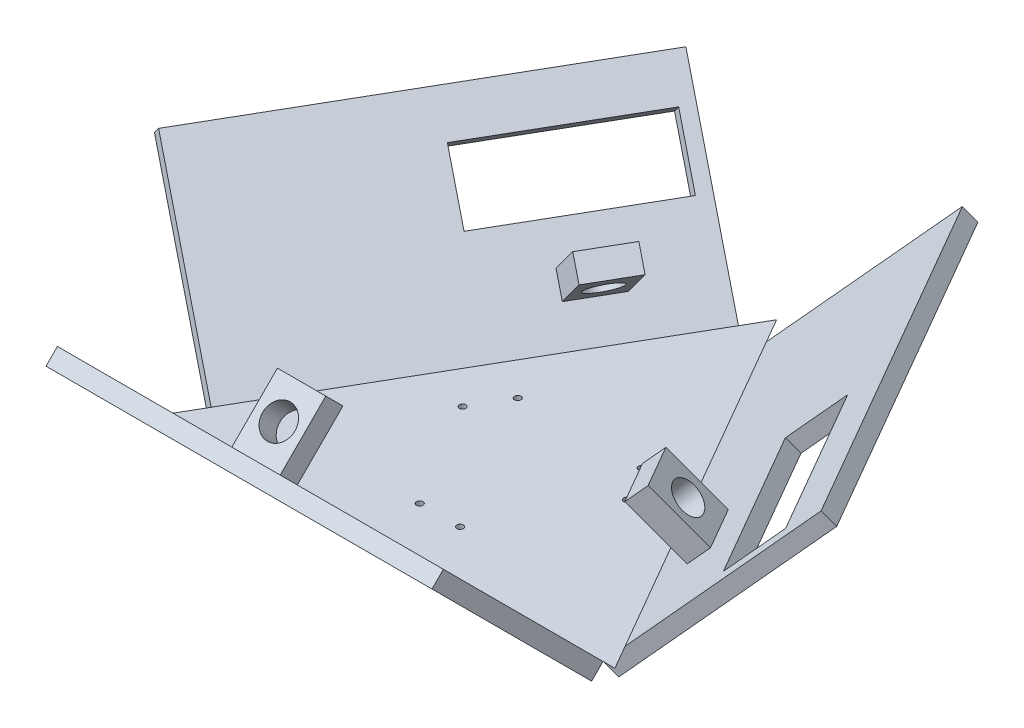
SolidWorks part; units mm, degrees
ref_plane "Front Plane" through (0, 0, 0) normal (0, 0, 1) x (1, 0, 0)
ref_plane "Top Plane" through (0, 0, 0) normal (0, 1, 0) x (1, 0, 0)
ref_plane "Right Plane" through (0, 0, 0) normal (1, 0, 0) x (0, 0, -1)
sketch "Sketch1" plane through (0, 0, 0) normal (0, 1, 0) x (1, 0, 0)
  line L0 (-40, 0) -> (40, 0) construction
  line L1 (-40, 0) -> (0, 69.282) construction
  line L2 (40, 0) -> (0, 69.282) construction
  line L3 (0, 69.282) -> (48.4974, 97.282) construction
  line L4 (40, 0) -> (88.4974, 28) construction
  line L5 (40, 0) -> (40, -56) construction
  line L6 (-40, 0) -> (-40, -56) construction
  line L7 (0, 69.282) -> (-48.4974, 97.282) construction
  line L8 (-40, 0) -> (-88.4974, 28) construction
  line L9 (-40, -56) -> (-136.9948, -56) construction
  line L10 (-88.4974, 28) -> (-136.9948, -56) construction
  line L11 (40, -56) -> (136.9948, -56) construction
  line L12 (88.4974, 28) -> (136.9948, -56) construction
  line L13 (-48.4974, 97.282) -> (0, 181.282) construction
  line L14 (48.4974, 97.282) -> (0, 181.282) construction
  line L15 (0, 181.282) -> (-136.9948, -56)
  line L16 (0, 181.282) -> (136.9948, -56)
  line L17 (136.9948, -56) -> (-136.9948, -56)
  line L18 (-24.2487, 83.282) -> (-38.2487, 59.0333) construction
  line L19 (-38.2487, 59.0333) -> (-50.7487, 37.3827) construction
  line L20 (64.2487, 14) -> (50.2487, 38.2487) construction
  line L21 (50.2487, 38.2487) -> (37.7487, 59.8993) construction
  line L22 (-40, -28) -> (-12, -28) construction
  line L23 (-12, -28) -> (13, -28) construction
  circle A0 centre (-38.2487, 59.0333) radius 2
  circle A1 centre (-50.7487, 37.3827) radius 2
  circle A2 centre (37.7487, 59.8993) radius 2
  circle A3 centre (50.2487, 38.2487) radius 2
  circle A4 centre (-12, -28) radius 2
  circle A5 centre (13, -28) radius 2
  dimension "D16" = 4
  dimension "D17" = 4
  dimension "D18" = 4
  dimension "D19" = 4
  dimension "D20" = 4
  dimension "D21" = 4
  dimension "D1" = 80
  dimension "D2" = 40
  dimension "D3" = 60
  dimension "D4" = 80
  dimension "D5" = 56
  dimension "D6" = 56
  dimension "D7" = 56
  dimension "D8" = 56
  dimension "D9" = 56
  dimension "D10" = 28
  dimension "D11" = 25
  dimension "D12" = 25
  dimension "D13" = 28
  dimension "D14" = 28
  dimension "D15" = 25
extrude "Boss-Extrude1" add sketch "Sketch1" along normal blind 10
chamfer "Chamfer2" distance 10 distance2 10 3 edges at (68.4974, 0, -62.641) (-68.4974, 0, -62.641) (0, 0, 56)
sketch "Sketch4" plane through (34.9186, -40.3205, -20.1603) normal (0.6124, -0.7071, -0.3536) x (0.7906, 0.5477, 0.2739)
  line L0 (107.2085, 41.1437) -> (215.652, -47.4001)
  line L1 (-44.1689, -144.255) -> (64.2746, -232.7988)
  line L2 (64.2746, -232.7988) -> (215.652, -47.4001)
  line L3 (-44.1689, -144.255) -> (107.2085, 41.1437)
  dimension "D1" = 140
  dimension "D2" = 140
extrude "Boss-Extrude2" add sketch "Sketch4" along normal blind 10
sketch "Sketch5" plane through (-34.9186, -40.3205, -20.1603) normal (-0.6124, -0.7071, -0.3536) x (0.7906, -0.5477, -0.2739)
  line L0 (44.1689, -144.255) -> (-64.2746, -232.7988)
  line L1 (-107.2085, 41.1437) -> (-215.652, -47.4001)
  line L2 (-107.2085, 41.1437) -> (44.1689, -144.255)
  line L3 (-64.2746, -232.7988) -> (-215.652, -47.4001)
  dimension "D1" = 140
  dimension "D2" = 90
  dimension "D3" = 140
  dimension "D7" = 90
extrude "Boss-Extrude3" add sketch "Sketch5" along normal blind 10
sketch "Sketch6" plane through (0, -23, 23) normal (0, -0.7071, 0.7071) x (1, 0, 0)
  line L0 (-119.6743, 32.5269) -> (119.6743, 32.5269)
  line L1 (119.6743, 32.5269) -> (119.6743, 172.5269)
  line L2 (119.6743, 172.5269) -> (-119.6743, 172.5269)
  line L3 (-119.6743, 172.5269) -> (-119.6743, 32.5269)
  dimension "D1" = 140
extrude "Boss-Extrude4" add sketch "Sketch6" along normal blind 10
sketch "Sketch7" plane through (0, 10, 0) normal (0, 1, 0) x (1, 0, 0)
  line L0 (-38.2487, 59.0333) -> (-14.7487, 99.7365) construction
  line L1 (-8.6603, 166.282) -> (-128.3346, -41) construction
  line L2 (-14.7487, 99.7365) -> (-38.9974, 113.7365) construction
  line L3 (50.2487, 38.2487) -> (73.7487, -2.4545) construction
  line L4 (128.3346, -41) -> (8.6603, 166.282) construction
  line L5 (-12, -28) -> (-59, -28) construction
  line L6 (-119.6743, -56) -> (119.6743, -56) construction
  line L7 (73.7487, -2.4545) -> (97.9974, 11.5455) construction
  line L8 (-59, -28) -> (-59, -56) construction
  dimension "D1" = 47
  dimension "D2" = 47
  dimension "D3" = 47
sketch "Sketch8" plane through (-34.9186, -40.3205, -20.1603) normal (0.6124, 0.7071, 0.3536) x (0.7906, -0.5477, -0.2739)
  line L0 (-5.1594, 106.2012) -> (-67.1271, 156.7976) construction
  line L1 (10.1769, 93.6792) -> (-5.1594, 106.2012) construction
  line L2 (-67.1271, 156.7976) -> (-33.9232, 197.4639) construction
  line L3 (-33.9232, 197.4639) -> (-49.4151, 210.113)
  line L4 (-49.4151, 210.113) -> (-115.823, 128.7804)
  line L5 (-115.823, 128.7804) -> (-84.8391, 103.4822)
  line L6 (-84.8391, 103.4822) -> (-18.4313, 184.8148)
  line L7 (-18.4313, 184.8148) -> (-33.9232, 197.4639)
  dimension "D1" = 80
  dimension "D2" = 52.5
  dimension "D3" = 20
  dimension "D4" = 105
  dimension "D5" = 40
extrude "Cut-Extrude1" cut sketch "Sketch8" against normal blind 10
sketch "Sketch10" plane through (34.9186, -40.3205, -20.1603) normal (-0.6124, 0.7071, 0.3536) x (0.7906, 0.5477, 0.2739)
  line L0 (79.7891, 14.7988) -> (141.7569, 65.3952) construction
  line L1 (64.4529, 2.2768) -> (79.7891, 14.7988) construction
  line L2 (141.7569, 65.3952) -> (174.9608, 24.7289) construction
  line L3 (174.9608, 24.7289) -> (190.4527, 37.378)
  line L4 (190.4527, 37.378) -> (124.0449, 118.7106)
  line L5 (124.0449, 118.7106) -> (93.061, 93.4124)
  line L6 (93.061, 93.4124) -> (159.4688, 12.0798)
  line L7 (159.4688, 12.0798) -> (174.9608, 24.7289)
  dimension "D1" = 80
  dimension "D2" = 52.5
  dimension "D3" = 20
  dimension "D4" = 105
  dimension "D5" = 40
extrude "Cut-Extrude2" cut sketch "Sketch10" against normal blind 10
sketch "Sketch11" plane through (0, -23, 23) normal (0, 0.7071, -0.7071) x (1, 0, 0)
  line L0 (-59, -46.669) -> (-59, -126.669) construction
  line L1 (-59, -126.669) -> (-111.5, -126.669) construction
  line L2 (-111.5, -126.669) -> (-111.5, -146.669)
  line L3 (-111.5, -146.669) -> (-6.5, -146.669)
  line L4 (-6.5, -146.669) -> (-6.5, -106.669)
  line L5 (-6.5, -106.669) -> (-111.5, -106.669)
  line L6 (-111.5, -106.669) -> (-111.5, -126.669)
  dimension "D1" = 80
  dimension "D2" = 52.5
  dimension "D3" = 20
  dimension "D4" = 105
  dimension "D5" = 40
extrude "Cut-Extrude3" cut sketch "Sketch11" against normal blind 10
sketch "Sketch12" plane through (-34.9186, -40.3205, -20.1603) normal (0.6124, 0.7071, 0.3536) x (0.7906, -0.5477, -0.2739)
  line L0 (-5.1594, 106.2012) -> (-28.3973, 125.1748) construction
  line L1 (-28.3973, 125.1748) -> (-18.9104, 136.7938) construction
  line L2 (-18.9104, 136.7938) -> (-24.7199, 141.5372)
  line L3 (-24.7199, 141.5372) -> (-43.6936, 118.2993)
  line L4 (-43.6936, 118.2993) -> (-32.0746, 108.8125)
  line L5 (-32.0746, 108.8125) -> (-13.101, 132.0504)
  line L6 (-13.101, 132.0504) -> (-18.9104, 136.7938)
  line L7 (10.1769, 93.6792) -> (-5.1594, 106.2012) construction
  dimension "D1" = 30
  dimension "D2" = 15
  dimension "D3" = 7.5
  dimension "D4" = 30
  dimension "D5" = 15
extrude "Boss-Extrude5" add sketch "Sketch12" along normal blind 40
sketch "Sketch13" plane through (-66.5428, 76.837, -38.4185) normal (-0.6124, 0.7071, -0.3536) x (0.7906, 0.5477, -0.2739)
  line L0 (36.779, 71.9587) -> (21.287, 84.6078) construction
  line L1 (46.2658, 83.5776) -> (27.2921, 60.3397) construction
  circle A0 centre (21.287, 84.6078) radius 10
  dimension "D2" = 20
  dimension "D1" = 20
extrude "Cut-Extrude4" cut sketch "Sketch13" against normal blind 15
sketch "Sketch14" plane through (34.9186, -40.3205, -20.1603) normal (-0.6124, 0.7071, 0.3536) x (0.7906, 0.5477, 0.2739)
  line L0 (79.7891, 14.7988) -> (103.027, 33.7724) construction
  line L1 (64.4529, 2.2768) -> (79.7891, 14.7988) construction
  line L2 (103.027, 33.7724) -> (112.5139, 22.1535) construction
  line L3 (112.5139, 22.1535) -> (118.3233, 26.8969)
  line L4 (118.3233, 26.8969) -> (99.3497, 50.1348)
  line L5 (99.3497, 50.1348) -> (87.7307, 40.648)
  line L6 (112.5139, 22.1535) -> (106.7044, 17.4101)
  line L7 (106.7044, 17.4101) -> (87.7307, 40.648)
  dimension "D1" = 30
  dimension "D2" = 15
  dimension "D3" = 7.5
  dimension "D4" = 30
  dimension "D6" = 7.5
extrude "Boss-Extrude6" add sketch "Sketch14" along normal blind 40
sketch "Sketch15" plane through (66.5428, 76.837, -38.4185) normal (0.6124, 0.7071, -0.3536) x (0.7906, -0.5477, 0.2739)
  line L0 (37.8508, -19.4437) -> (53.3427, -6.7946) construction
  line L2 (47.3376, -31.0627) -> (28.364, -7.8248) construction
  circle A0 centre (53.3427, -6.7946) radius 10
  dimension "D2" = 20
  dimension "D1" = 20
extrude "Cut-Extrude5" cut sketch "Sketch15" against normal blind 15
sketch "Sketch16" plane through (0, -23, 23) normal (0, 0.7071, -0.7071) x (1, 0, 0)
  line L0 (-59, -46.669) -> (-59, -76.669) construction
  line L1 (-59, -76.669) -> (-74, -76.669) construction
  line L2 (-74, -76.669) -> (-74, -84.169)
  line L3 (-74, -84.169) -> (-44, -84.169)
  line L4 (-44, -84.169) -> (-44, -69.169)
  line L5 (-44, -69.169) -> (-74, -69.169)
  line L6 (-74, -69.169) -> (-74, -76.669)
  dimension "D1" = 30
  dimension "D2" = 15
  dimension "D3" = 7.5
  dimension "D4" = 30
  dimension "D5" = 15
extrude "Boss-Extrude7" add sketch "Sketch16" along normal blind 40
sketch "Sketch17" plane through (0, 59.5165, 59.5165) normal (0, 0.7071, 0.7071) x (1, 0, 0)
  line L0 (-59, 7.4731) -> (-59, -12.5269) construction
  line L1 (-74, 7.4731) -> (-44, 7.4731) construction
  circle A0 centre (-59, -12.5269) radius 10
  dimension "D2" = 20
  dimension "D1" = 20
extrude "Cut-Extrude6" cut sketch "Sketch17" against normal blind 15
